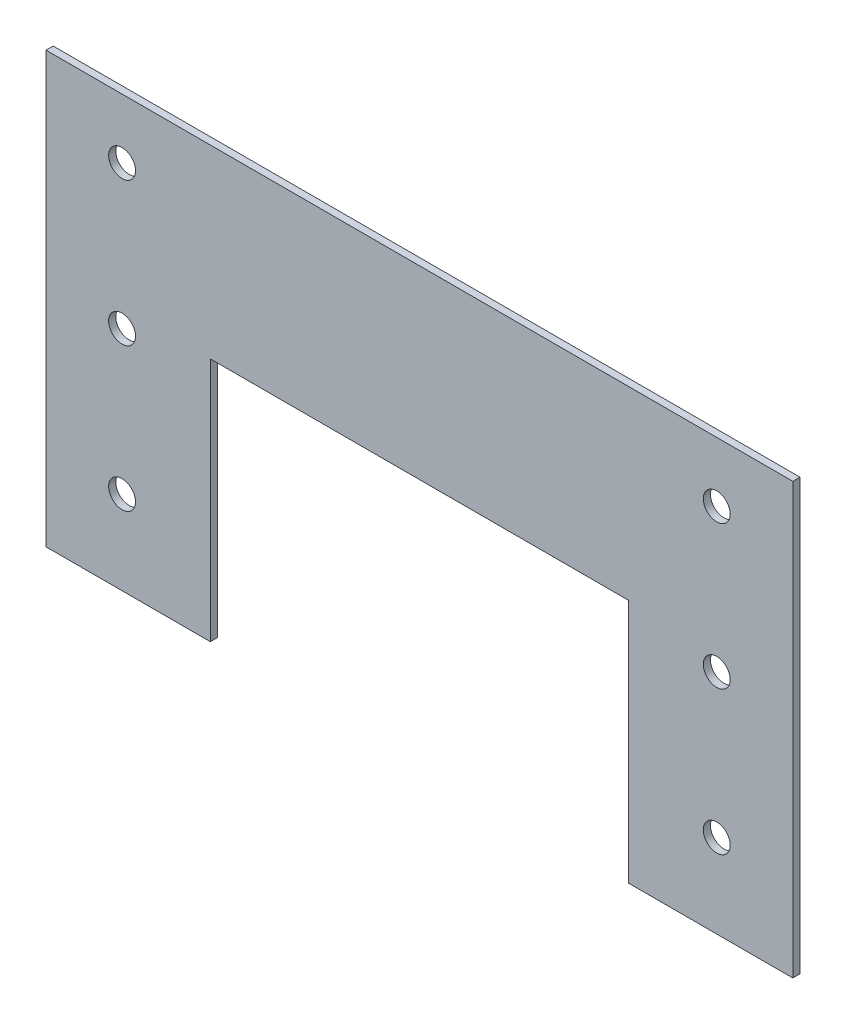
SolidWorks part; units mm, degrees
ref_plane "Спереди" through (0, 0, 0) normal (0, 0, 1) x (1, 0, 0)
ref_plane "Сверху" through (0, 0, 0) normal (0, 1, 0) x (1, 0, 0)
ref_plane "Справа" through (0, 0, 0) normal (1, 0, 0) x (0, 0, -1)
sketch "Эскиз1" plane through (0, 0, 0) normal (0, 0, 1) x (1, 0, 0)
  line L0 (97.5, 0) -> (125, 0)
  line L1 (0, 0) -> (27.5, 0)
  line L2 (0, 0) -> (0, 72)
  line L3 (0, 72) -> (125, 72)
  line L4 (125, 0) -> (125, 72)
  line L5 (62.5, 72) -> (62.5, 41) construction
  line L6 (97.5, 0) -> (97.5, 41)
  line L7 (97.5, 41) -> (27.5, 41)
  line L8 (27.5, 0) -> (27.5, 41)
  line L9 (12.7317, 62) -> (12.7317, 14) construction
  line L10 (12.7317, 14) -> (112.2683, 14) construction
  line L11 (112.2683, 14) -> (112.2683, 62) construction
  line L12 (112.2683, 62) -> (12.7317, 62) construction
  line L14 (112.2683, 38) -> (12.7317, 38) construction
  circle A0 centre (112.2683, 62) radius 2.25
  circle A1 centre (112.2683, 38) radius 2.25
  circle A2 centre (112.2683, 14) radius 2.25
  circle A3 centre (12.7317, 62) radius 2.25
  circle A4 centre (12.7317, 38) radius 2.25
  circle A5 centre (12.7317, 14) radius 2.25
  point P29 (12.7317, 38)
  point P30 (112.2683, 38)
  point P31 (12.7317, 38)
  point P32 (103.6491, 38)
  point P33 (0, 0)
  dimension "D9" = 4.5
  dimension "D1" = 72
  dimension "D2" = 125
  dimension "D3" = 70
  dimension "D4" = 12.7317
  dimension "D5" = 12.7317
  dimension "D6" = 14
  dimension "D7" = 24
  dimension "D8" = 24
  dimension "D10" = 41
base flange "Базовая кромка1" sketch "Эскиз1" thickness 1.2 reverse thickness direction no parameters "D1"=0.7366
sketch "Сгиб-Линии1" plane through (0, 0, 0) normal (0, 1, 0) x (1, 0, 0)
sketch "Граничная рамка1" plane through (0, 0, 0) normal (0, 1, 0) x (1, 0, 0)
sheet metal parameters "Листовой металл3" thickness 1.2 parameters "D1"=0.7366
flat pattern "Развертка3" [suppressed]
sketch "Сгиб-Линии2" plane through (0, 0, 0) normal (0, 1, 0) x (1, 0, 0)
sketch "Граничная рамка2" [suppressed] plane through (0, 0, 0) normal (0, 1, 0) x (1, 0, 0)
